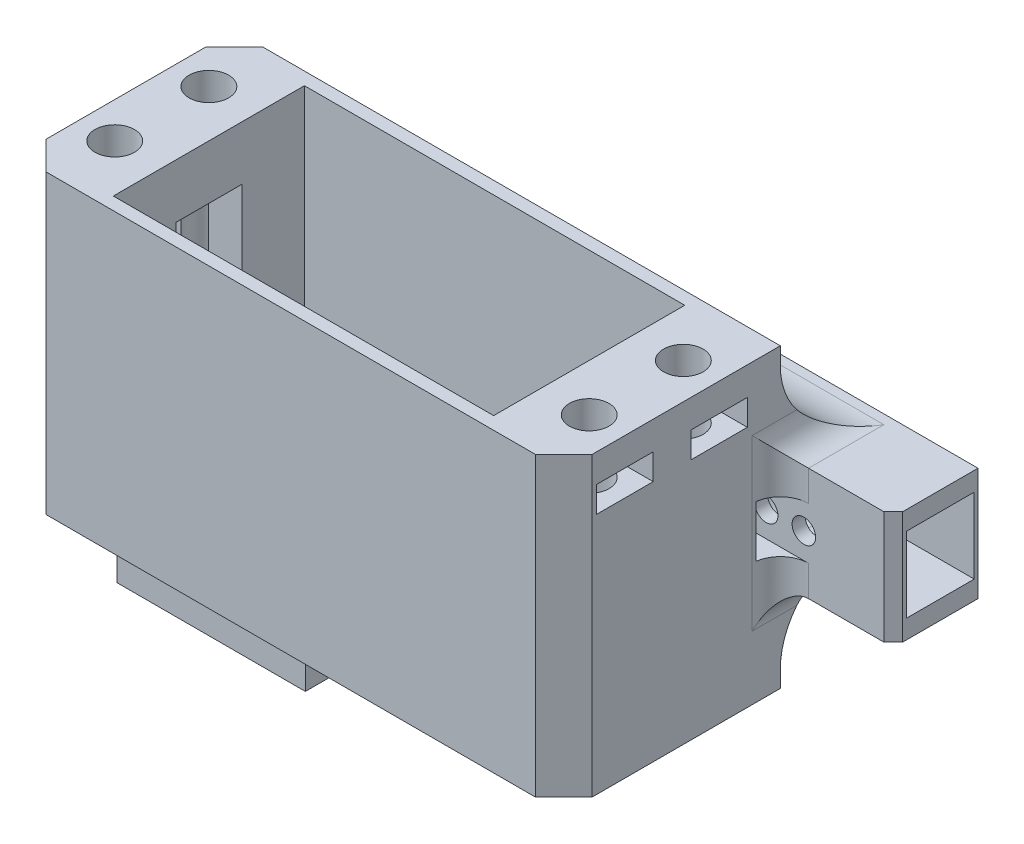
SolidWorks part; units mm, degrees
ref_plane "Front Plane" through (0, 0, 0) normal (0, 0, 1) x (1, 0, 0)
ref_plane "Top Plane" through (0, 0, 0) normal (0, 1, 0) x (1, 0, 0)
ref_plane "Right Plane" through (0, 0, 0) normal (1, 0, 0) x (0, 0, -1)
sketch "Sketch1" plane through (0, 0, 0) normal (0, 1, 0) x (1, 0, 0)
  line L0 (9.75, 0.5273) -> (50.15, 0.5273)
  line L1 (50.15, 0.5273) -> (50.15, -19.7727)
  line L2 (50.15, -19.7727) -> (9.75, -19.7727)
  line L4 (0.95, -21.1227) -> (58.95, -21.1227)
  line L5 (58.95, -21.1227) -> (58.95, 1.8773)
  line L6 (58.95, 1.8773) -> (0.95, 1.8773)
  line L8 (55.15, -4.6227) -> (55.15, -14.6227) construction
  line L9 (0.95, 1.8773) -> (0.95, -21.1227)
  line L10 (9.75, 0.5273) -> (9.75, -19.7727)
  line L11 (29.95, 0.5273) -> (29.95, -19.7727) construction
  circle A0 centre (55.15, -4.6227) radius 2.1
  circle A1 centre (55.15, -14.6227) radius 2.1
  circle A2 centre (4.75, -14.6227) radius 2.1
  circle A3 centre (4.75, -4.6227) radius 2.1
  point P13 (55.15, -9.6227)
  point P14 (50.15, -9.6227)
  point P20 (0.95, -9.6227)
  point P22 (29.95, 1.8773)
  dimension "D1" = 4.2
  dimension "D2" = 10
  dimension "D3" = 23
  dimension "D4" = 40.4
  dimension "D5" = 5
  dimension "D6" = 20.3
  dimension "D7" = 58
extrude "Boss-Extrude1" add sketch "Sketch1" along normal blind 28.35
sketch "Sketch11" plane through (0, 0, 0) normal (0, -1, 0) x (1, 0, 0)
  line L1 (0.95, 21.1227) -> (58.95, 21.1227)
  line L2 (0.95, 21.1227) -> (0.95, -1.8773)
  line L3 (0.95, -1.8773) -> (58.95, -1.8773)
  line L4 (58.95, 21.1227) -> (58.95, -1.8773)
extrude "Boss-Extrude5" add sketch "Sketch11" along normal blind 3.175
sketch "Sketch14" plane through (0, 0, -1.8773) normal (0, 0, -1) x (-1, 0, 0)
  line L7 (-58.95, 28.35) -> (-58.95, -3.175) construction
  line L8 (-46.95, 6.5875) -> (-70.95, 6.5875)
  line L9 (-46.95, 6.5875) -> (-46.95, 18.5875)
  line L10 (-46.95, 18.5875) -> (-70.95, 18.5875)
  line L11 (-70.95, 6.5875) -> (-70.95, 18.5875)
  line L12 (-46.95, 6.5875) -> (-70.95, 18.5875) construction
  line L13 (-46.95, 18.5875) -> (-70.95, 6.5875) construction
  point P0 (-58.95, 12.5875)
  point P5 (-58.95, 12.5875)
  dimension "D1" = 24
  dimension "D2" = 12
  dimension "D3" = 0
extrude "Boss-Extrude7" add sketch "Sketch14" along normal blind 10
ref_plane "Plane1" through (0, 0, -6.8773) normal (0, 0, 1) x (1, 0, 0)
sketch "Sketch16" plane through (0, 0, -6.8773) normal (0, 0, 1) x (1, 0, 0)
  line L0 (70.95, 18.5875) -> (70.95, 6.5875) construction
  line L1 (57.45, 8.5875) -> (70.95, 8.5875)
  line L3 (57.45, 16.5875) -> (70.95, 16.5875)
  line L4 (70.95, 8.5875) -> (70.95, 16.5875)
  line L5 (46.95, 6.5875) -> (46.95, 18.5875) construction
  arc A0 (57.45, 16.5875) -> (57.45, 8.5875) centre (57.45, 12.5875) ccw
  point P9 (46.95, 12.5875)
  dimension "D2" = 4
  dimension "D1" = 13.5
extrude "Cut-Extrude1" cut sketch "Sketch16" against normal mid plane 7.2
sketch "Sketch18" plane through (0, 0, -11.8773) normal (0, 0, -1) x (-1, 0, 0)
  arc A0 (-60.2, 12.5875) -> (-62.7, 12.5875) centre (-61.45, 12.5875) ccw construction
  arc A1 (-62.7, 12.5875) -> (-60.2, 12.5875) centre (-61.45, 12.5875) ccw construction
  arc A2 (-56.2, 12.5875) -> (-58.7, 12.5875) centre (-57.45, 12.5875) ccw construction
  arc A3 (-58.7, 12.5875) -> (-56.2, 12.5875) centre (-57.45, 12.5875) ccw construction
  arc A4 (-60.2, 12.5875) -> (-62.7, 12.5875) centre (-61.45, 12.5875) ccw
  arc A5 (-62.7, 12.5875) -> (-60.2, 12.5875) centre (-61.45, 12.5875) ccw
  arc A6 (-56.2, 12.5875) -> (-58.7, 12.5875) centre (-57.45, 12.5875) ccw
  arc A7 (-58.7, 12.5875) -> (-56.2, 12.5875) centre (-57.45, 12.5875) ccw
extrude "Cut-Extrude2" cut sketch "Sketch18" against normal up to surface (10 mm away) up to face at (64.95, 12.5875, -1.8773)
fillet "Fillet1" radius 8 3 edges at (52.95, 6.5875, -1.8773) (46.95, 12.5875, -1.8773) (52.95, 18.5875, -1.8773)
chamfer "Chamfer2" distance 3 angle 45 3 edges at (0.95, 12.5875, -1.8773) (0.95, 12.5875, 21.1227) (58.95, 12.5875, 21.1227)
fillet "Fillet2" radius 3 2 edges at (58.95, 6.5875, -5.8773) (58.95, 18.5875, -5.8773)
fillet "Fillet3" radius 3 1 edges at (58.95, 12.5875, -1.8773)
chamfer "Chamfer3" distance 1 angle 45 5 edges at (70.95, 12.5875, -1.8773) (70.95, 12.5875, -11.8773) (58.95, 6.5875, -11.8773) (46.95, 12.5875, -11.8773) (58.95, 18.5875, -11.8773)
ref_plane "Plane2" through (0, 25.35, 0) normal (0, 1, 0) x (1, 0, 0)
sketch "Sketch19" plane through (0, 25.35, 0) normal (0, 1, 0) x (1, 0, 0)
  line L0 (0.95, -1.1227) -> (0.95, -18.1227) construction
  line L1 (0.95, -1.6227) -> (8.95, -1.6227)
  line L2 (0.95, -1.6227) -> (0.95, -7.6227)
  line L3 (0.95, -7.6227) -> (8.95, -7.6227)
  line L4 (8.95, -1.6227) -> (8.95, -7.6227)
  line L5 (-0.5892, -9.6227) -> (60.8708, -9.6227) construction
  line L6 (29.95, -22.0073) -> (29.95, 3.0189) construction
  line L7 (9.75, 0.5273) -> (9.75, -19.7727) construction
  line L8 (50.15, 0.5273) -> (9.75, 0.5273) construction
  line L9 (8.95, -17.6227) -> (8.95, -11.6227)
  line L10 (0.95, -11.6227) -> (8.95, -11.6227)
  line L11 (0.95, -17.6227) -> (0.95, -11.6227)
  line L12 (0.95, -17.6227) -> (8.95, -17.6227)
  line L37 (60.4892, -9.6227) -> (-0.9708, -9.6227) construction
  line L38 (58.95, -17.6227) -> (50.95, -17.6227)
  line L39 (58.95, -17.6227) -> (58.95, -11.6227)
  line L40 (58.95, -11.6227) -> (50.95, -11.6227)
  line L41 (50.95, -17.6227) -> (50.95, -11.6227)
  line L42 (50.95, -1.6227) -> (50.95, -7.6227)
  line L43 (58.95, -7.6227) -> (50.95, -7.6227)
  line L44 (58.95, -1.6227) -> (58.95, -7.6227)
  line L45 (58.95, -1.6227) -> (50.95, -1.6227)
  circle A0 centre (4.75, -4.6227) radius 2.1 construction
  circle A1 centre (4.75, -4.6227) radius 2.1 construction
  circle A2 centre (4.75, -14.6227) radius 2.1 construction
  circle A3 centre (4.75, -4.6227) radius 2.1 construction
  circle A4 centre (4.75, -14.6227) radius 2.1 construction
  circle A5 centre (4.75, -4.6227) radius 2.1 construction
  circle A6 centre (4.75, -14.6227) radius 2.1 construction
  circle A7 centre (4.75, -4.6227) radius 2.1 construction
  circle A8 centre (4.75, -14.6227) radius 2.1 construction
  circle A9 centre (55.15, -14.6227) radius 2.1 construction
  circle A10 centre (55.15, -4.6227) radius 2.1 construction
  circle A11 centre (55.15, -14.6227) radius 2.1 construction
  circle A12 centre (55.15, -4.6227) radius 2.1 construction
  circle A13 centre (55.15, -14.6227) radius 2.1 construction
  circle A14 centre (55.15, -4.6227) radius 2.1 construction
  circle A15 centre (55.15, -14.6227) radius 2.1 construction
  circle A16 centre (55.15, -4.6227) radius 2.1 construction
  point P11 (0.95, -4.6227)
  point P18 (9.75, -9.6227)
  point P21 (29.95, 0.5273)
  point P28 (0.95, -14.6227)
  point P55 (58.95, -14.6227)
  point P56 (58.95, -4.6227)
  dimension "D1" = 6
  dimension "D2" = 8
extrude "Cut-Extrude3" cut sketch "Sketch19" against normal blind 2.75
sketch "Sketch20" plane through (0, 0, 0) normal (0, 1, 0) x (1, 0, 0)
  line L0 (0.95, -1.1227) -> (0.95, -18.1227) construction
  line L1 (0.95, -13.1227) -> (9.75, -13.1227)
  line L2 (0.95, -13.1227) -> (0.95, -6.1227)
  line L3 (0.95, -6.1227) -> (9.75, -6.1227)
  line L4 (9.75, -13.1227) -> (9.75, -6.1227)
  line L5 (9.75, 0.5273) -> (9.75, -19.7727) construction
  point P6 (0.95, -9.6227)
  dimension "D1" = 7
extrude "Cut-Extrude4" cut sketch "Sketch20" along normal blind 3
sketch "Sketch21" plane through (0, -3.175, 0) normal (0, -1, 0) x (1, 0, 0)
  line L0 (0.95, 18.1227) -> (0.95, 1.1227) construction
  line L1 (30, -0.3773) -> (10, -0.3773)
  line L2 (30, -0.3773) -> (30, 19.6227)
  line L3 (30, 19.6227) -> (10, 19.6227)
  line L4 (10, -0.3773) -> (10, 19.6227)
  line L5 (30, -0.3773) -> (10, 19.6227) construction
  line L6 (30, 19.6227) -> (10, -0.3773) construction
  point P0 (20, 9.6227)
  point P7 (0.95, 9.6227)
  dimension "D1" = 19.05
  dimension "D2" = 20
  dimension "D3" = 20
extrude "Boss-Extrude8" add sketch "Sketch21" along normal blind 6
sketch "Sketch13" plane through (0, -9.175, 0) normal (0, -1, 0) x (1, 0, 0)
  line L0 (0.95, 18.1227) -> (0.95, 1.1227) construction
  circle A0 centre (20, 9.6227) radius 2.95
  point P2 (0.95, 9.6227)
  dimension "D2" = 5.9
  dimension "D1" = 19.05
extrude "Boss-Extrude6" add sketch "Sketch13" along normal blind 5
fillet "Fillet4" radius 1 4 edges at (20, -3.175, 19.6227) (30, -3.175, 9.6227) (20, -3.175, -0.3773) (10, -3.175, 9.6227)
chamfer "Chamfer4" distance 2 angle 45 4 edges at (20, -9.175, 19.6227) (30, -9.175, 9.6227) (20, -9.175, -0.3773) (10, -9.175, 9.6227)
fillet "Fillet5" radius 1 1 edges at (20, -14.175, 6.6727)
sketch "Sketch22" plane through (0, 28.35, 0) normal (0, 1, 0) x (1, 0, 0)
  line L0 (9.75, 0.5273) -> (9.75, -19.7727) construction
  line L2 (9.75, -6.1227) -> (2.75, -6.1227)
  line L3 (9.75, -6.1227) -> (9.75, -13.1227)
  line L4 (9.75, -13.1227) -> (2.75, -13.1227)
  line L5 (2.75, -6.1227) -> (2.75, -13.1227)
  point P0 (9.75, -9.6227)
  dimension "D1" = 7
  dimension "D2" = 7
extrude "Cut-Extrude5" cut sketch "Sketch22" against normal up to surface (28.35 mm away) from surface up to face at (13.35, 0, 9.6227) starting at face at (4.75, 22.6, 16.7227)
sketch "Sketch23" plane through (0, 0, -11.8773) normal (0, 0, -1) x (-1, 0, 0)
  line L0 (-47.95, 17.5875) -> (-69.95, 17.5875) construction
  line L14 (-69.95, 17.5875) -> (-69.95, 7.5875) construction
  line L15 (-64.6254, 15.3375) -> (-54.2746, 15.3375)
  line L16 (-64.6254, 15.3375) -> (-64.6254, 9.8375)
  line L17 (-64.6254, 9.8375) -> (-54.2746, 9.8375)
  line L18 (-54.2746, 15.3375) -> (-54.2746, 9.8375)
  dimension "D1" = 5.5
  dimension "D2" = 10.3509
  dimension "D3" = 2.25
  dimension "D4" = 5.3246
extrude "Cut-Extrude6" cut sketch "Sketch23" against normal blind 2.6 from surface starting at face at (64.7417, 12.5875, -1.8773)
